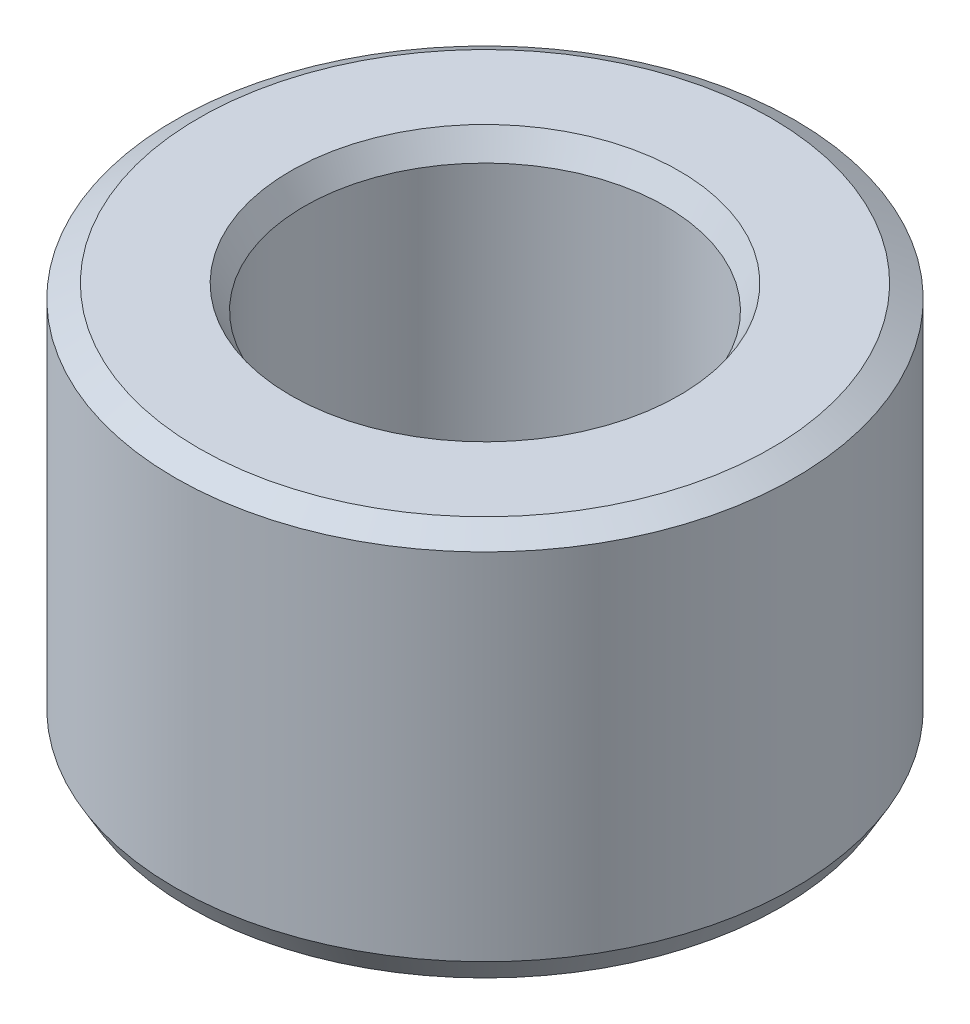
SolidWorks part; units mm, degrees
ref_plane "Front Plane" through (0, 0, 0) normal (0, 0, 1) x (1, 0, 0)
ref_plane "Top Plane" through (0, 0, 0) normal (0, 1, 0) x (1, 0, 0)
ref_plane "Right Plane" through (0, 0, 0) normal (1, 0, 0) x (0, 0, -1)
sketch "Sketch1" plane through (0, 0, 0) normal (0, 1, 0) x (1, 0, 0)
  circle A0 centre (0, 0) radius 57.5
  dimension "SLEEVE_OD" = 115
extrude "Boss-Extrude1" add sketch "Sketch1" along normal blind 72.7995
sketch "Sketch2" plane through (0, 0, 0) normal (0, 1, 0) x (1, 0, 0)
  circle A0 centre (0, 0) radius 33.5246
  dimension "BORE_D" = 67.0492
extrude "Cut-Extrude1" cut sketch "Sketch2" along normal through all
chamfer "Chamfer1" distance 2.5428 angle 60 4 edges at (0, 72.7995, 33.5246) (0, 0, 33.5246) (0, 0, 57.5) (0, 72.7995, 57.5) first distance on face at (0, 72.7995, 33.5246) first distance on face at (0, 0, 33.5246) first distance on face at (0, 72.7995, 57.5)
